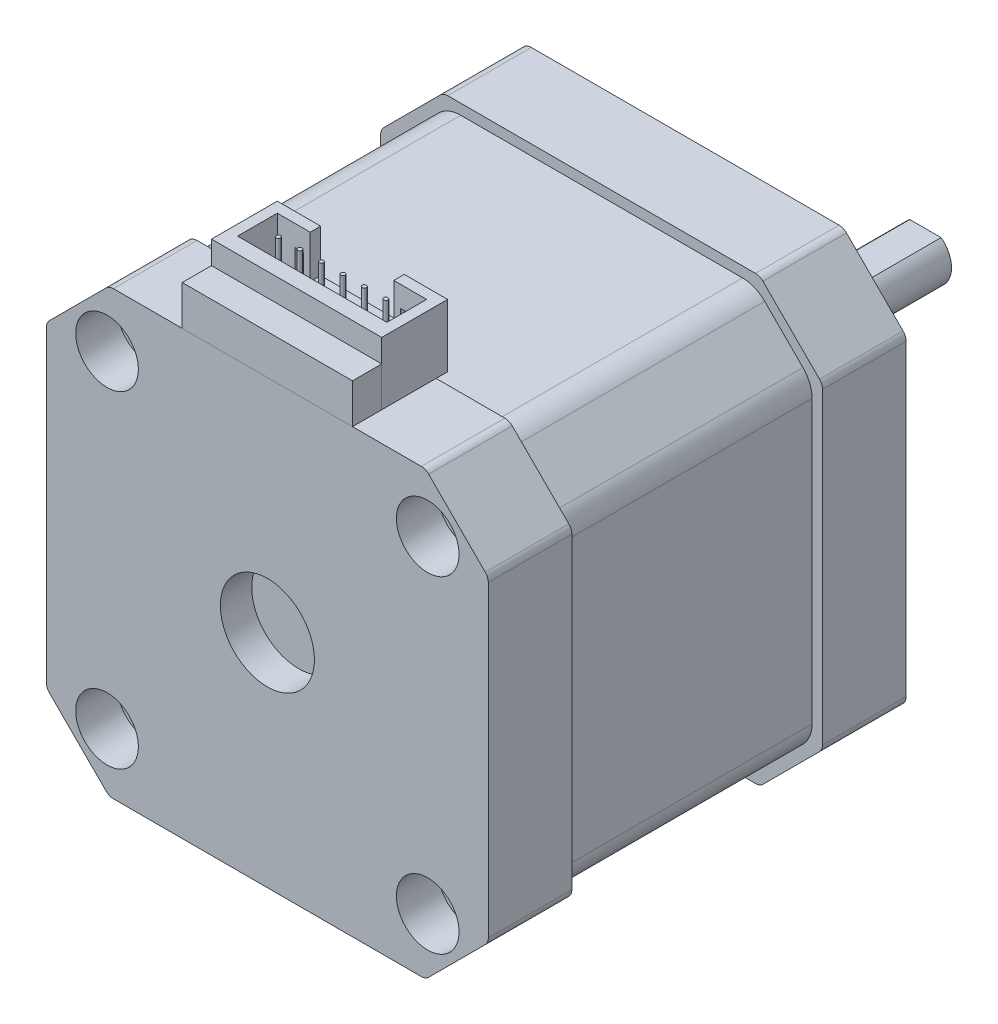
SolidWorks part; units mm, degrees
ref_plane "Front Plane" through (0, 0, 0) normal (0, 0, 1) x (1, 0, 0)
ref_plane "Top Plane" through (0, 0, 0) normal (0, 1, 0) x (1, 0, 0)
ref_plane "Right Plane" through (0, 0, 0) normal (1, 0, 0) x (0, 0, -1)
sketch "Sketch1" plane through (0, 0, 0) normal (0, 0, 1) x (1, 0, 0)
  line L1 (-21.15, 21.15) -> (21.15, 21.15)
  line L2 (-21.15, 21.15) -> (-21.15, -21.15)
  line L3 (-21.15, -21.15) -> (21.15, -21.15)
  line L4 (21.15, 21.15) -> (21.15, -21.15)
  line L5 (-21.15, 21.15) -> (21.15, -21.15) construction
  line L6 (-21.15, -21.15) -> (21.15, 21.15) construction
  point P0 (0, 0)
  dimension "D1" = 42.3
  dimension "D2" = 42.3
extrude "Boss-Extrude1" add sketch "Sketch1" along normal blind 8
chamfer "Chamfer1" distance 6 angle 45 4 edges at (-21.15, -21.15, 4) (21.15, -21.15, 4) (21.15, 21.15, 4) (-21.15, 21.15, 4)
fillet "Fillet1" radius 1 8 edges at (-15.15, 21.15, 4) (-21.15, 15.15, 4) (-21.15, -15.15, 4) (-15.15, -21.15, 4) (15.15, -21.15, 4) (21.15, -15.15, 4) (21.15, 15.15, 4) (15.15, 21.15, 4)
sketch "Sketch3" plane through (0, 0, 0) normal (0, 0, -1) x (-1, 0, 0)
  line L0 (-14.7358, 21.15) -> (14.7358, 21.15) construction
  line L1 (-15.4429, 20.8571) -> (-20.8571, 15.4429) construction
  line L2 (-21.15, -14.7358) -> (-21.15, 14.7358) construction
  line L3 (20.8571, 15.4429) -> (15.4429, 20.8571) construction
  line L4 (21.15, 14.7358) -> (21.15, -14.7358) construction
  line L5 (15.4429, -20.8571) -> (20.8571, -15.4429) construction
  line L6 (14.7358, -21.15) -> (-14.7358, -21.15) construction
  line L7 (-20.8571, -15.4429) -> (-15.4429, -20.8571) construction
  line L8 (-14.7358, 21.15) -> (14.7358, 21.15)
  line L9 (-15.4429, 20.8571) -> (-20.8571, 15.4429)
  line L10 (-21.15, -14.7358) -> (-21.15, 14.7358)
  line L11 (20.8571, 15.4429) -> (15.4429, 20.8571)
  line L12 (21.15, 14.7358) -> (21.15, -14.7358)
  line L13 (15.4429, -20.8571) -> (20.8571, -15.4429)
  line L14 (14.7358, -21.15) -> (-14.7358, -21.15)
  line L15 (-20.8571, -15.4429) -> (-15.4429, -20.8571)
  line L16 (-14.7358, 20.15) -> (14.7358, 20.15)
  line L17 (20.15, 14.7358) -> (14.7358, 20.15)
  line L18 (20.15, 14.7358) -> (20.15, -14.7358)
  line L19 (14.7358, -20.15) -> (20.15, -14.7358)
  line L20 (14.7358, -20.15) -> (-14.7358, -20.15)
  line L21 (-20.15, -14.7358) -> (-14.7358, -20.15)
  line L22 (-20.15, -14.7358) -> (-20.15, 14.7358)
  line L23 (-14.7358, 20.15) -> (-20.15, 14.7358)
  arc A0 (20.8571, -15.4429) -> (21.15, -14.7358) centre (20.15, -14.7358) ccw construction
  arc A1 (14.7358, -21.15) -> (15.4429, -20.8571) centre (14.7358, -20.15) ccw construction
  arc A2 (-15.4429, -20.8571) -> (-14.7358, -21.15) centre (-14.7358, -20.15) ccw construction
  arc A3 (-21.15, -14.7358) -> (-20.8571, -15.4429) centre (-20.15, -14.7358) ccw construction
  arc A4 (15.4429, 20.8571) -> (14.7358, 21.15) centre (14.7358, 20.15) ccw construction
  arc A5 (21.15, 14.7358) -> (20.8571, 15.4429) centre (20.15, 14.7358) ccw construction
  arc A6 (-14.7358, 21.15) -> (-15.4429, 20.8571) centre (-14.7358, 20.15) ccw construction
  arc A7 (-20.8571, 15.4429) -> (-21.15, 14.7358) centre (-20.15, 14.7358) ccw construction
  arc A8 (20.8571, -15.4429) -> (21.15, -14.7358) centre (20.15, -14.7358) ccw
  arc A9 (14.7358, -21.15) -> (15.4429, -20.8571) centre (14.7358, -20.15) ccw
  arc A10 (-15.4429, -20.8571) -> (-14.7358, -21.15) centre (-14.7358, -20.15) ccw
  arc A11 (-21.15, -14.7358) -> (-20.8571, -15.4429) centre (-20.15, -14.7358) ccw
  arc A12 (15.4429, 20.8571) -> (14.7358, 21.15) centre (14.7358, 20.15) ccw
  arc A13 (21.15, 14.7358) -> (20.8571, 15.4429) centre (20.15, 14.7358) ccw
  arc A14 (-14.7358, 21.15) -> (-15.4429, 20.8571) centre (-14.7358, 20.15) ccw
  arc A15 (-20.8571, 15.4429) -> (-21.15, 14.7358) centre (-20.15, 14.7358) ccw
  arc A16 (14.7358, 20.15) -> (14.7358, 20.15) centre (14.7358, 20.15) ccw
  arc A17 (20.15, 14.7358) -> (20.15, 14.7358) centre (20.15, 14.7358) ccw
  arc A18 (20.15, -14.7358) -> (20.15, -14.7358) centre (20.15, -14.7358) ccw
  arc A19 (14.7358, -20.15) -> (14.7358, -20.15) centre (14.7358, -20.15) ccw
  arc A20 (-14.7358, -20.15) -> (-14.7358, -20.15) centre (-14.7358, -20.15) ccw
  arc A21 (-20.15, -14.7358) -> (-20.15, -14.7358) centre (-20.15, -14.7358) ccw
  arc A22 (-20.15, 14.7358) -> (-20.15, 14.7358) centre (-20.15, 14.7358) ccw
  arc A23 (-14.7358, 20.15) -> (-14.7358, 20.15) centre (-14.7358, 20.15) ccw
  dimension "D1" = 1
extrude "Boss-Extrude4" add sketch "Sketch3" along normal blind 24 separate body contours L16 A16 L17 A17 L18 A18 L19 A19 L20 A20 L21 A21 L22 A22 L23 A23
fillet "Fillet2" radius 3 8 edges at (20.15, -14.7358, -12) (14.7358, -20.15, -12) (-14.7358, -20.15, -12) (-20.15, -14.7358, -12) (-20.15, 14.7358, -12) (-14.7358, 20.15, -12) (20.15, 14.7358, -12) (14.7358, 20.15, -12)
sketch "Sketch6" plane through (0, 0, -24) normal (0, 0, -1) x (-1, 0, 0)
  line L0 (15.4429, -20.8571) -> (20.8571, -15.4429) construction
  line L1 (14.7358, -21.15) -> (-14.7358, -21.15) construction
  line L2 (-20.8571, -15.4429) -> (-15.4429, -20.8571) construction
  line L3 (-21.15, -14.7358) -> (-21.15, 14.7358) construction
  line L4 (-15.4429, 20.8571) -> (-20.8571, 15.4429) construction
  line L5 (-14.7358, 21.15) -> (14.7358, 21.15) construction
  line L6 (20.8571, 15.4429) -> (15.4429, 20.8571) construction
  line L7 (21.15, 14.7358) -> (21.15, -14.7358) construction
  line L8 (15.4429, -20.8571) -> (20.8571, -15.4429)
  line L9 (14.7358, -21.15) -> (-14.7358, -21.15)
  line L10 (-20.8571, -15.4429) -> (-15.4429, -20.8571)
  line L11 (-21.15, -14.7358) -> (-21.15, 14.7358)
  line L12 (-15.4429, 20.8571) -> (-20.8571, 15.4429)
  line L13 (-14.7358, 21.15) -> (14.7358, 21.15)
  line L14 (20.8571, 15.4429) -> (15.4429, 20.8571)
  line L15 (21.15, 14.7358) -> (21.15, -14.7358)
  arc A0 (20.8571, -15.4429) -> (21.15, -14.7358) centre (20.15, -14.7358) ccw construction
  arc A1 (14.7358, -21.15) -> (15.4429, -20.8571) centre (14.7358, -20.15) ccw construction
  arc A2 (-15.4429, -20.8571) -> (-14.7358, -21.15) centre (-14.7358, -20.15) ccw construction
  arc A3 (-21.15, -14.7358) -> (-20.8571, -15.4429) centre (-20.15, -14.7358) ccw construction
  arc A4 (-20.8571, 15.4429) -> (-21.15, 14.7358) centre (-20.15, 14.7358) ccw construction
  arc A5 (-14.7358, 21.15) -> (-15.4429, 20.8571) centre (-14.7358, 20.15) ccw construction
  arc A6 (15.4429, 20.8571) -> (14.7358, 21.15) centre (14.7358, 20.15) ccw construction
  arc A7 (21.15, 14.7358) -> (20.8571, 15.4429) centre (20.15, 14.7358) ccw construction
  arc A8 (20.8571, -15.4429) -> (21.15, -14.7358) centre (20.15, -14.7358) ccw
  arc A9 (14.7358, -21.15) -> (15.4429, -20.8571) centre (14.7358, -20.15) ccw
  arc A10 (-15.4429, -20.8571) -> (-14.7358, -21.15) centre (-14.7358, -20.15) ccw
  arc A11 (-21.15, -14.7358) -> (-20.8571, -15.4429) centre (-20.15, -14.7358) ccw
  arc A12 (-20.8571, 15.4429) -> (-21.15, 14.7358) centre (-20.15, 14.7358) ccw
  arc A13 (-14.7358, 21.15) -> (-15.4429, 20.8571) centre (-14.7358, 20.15) ccw
  arc A14 (15.4429, 20.8571) -> (14.7358, 21.15) centre (14.7358, 20.15) ccw
  arc A15 (21.15, 14.7358) -> (20.8571, 15.4429) centre (20.15, 14.7358) ccw
extrude "Boss-Extrude5" add sketch "Sketch6" along normal blind 8 separate body
sketch "Sketch7" plane through (0, 0, 8) normal (0, 0, 1) x (1, 0, 0)
  line L0 (-15.35, 15.65) -> (15.35, 15.65) construction
  line L1 (-15.35, -15.65) -> (15.35, -15.65) construction
  line L2 (14.7358, 21.15) -> (-14.7358, 21.15) construction
  line L3 (15.35, 15.65) -> (20.65, 15.65) construction
  line L4 (20.8571, 15.4429) -> (15.4429, 20.8571) construction
  line L5 (-15.35, 15.65) -> (-20.65, 15.65) construction
  line L6 (-15.4429, 20.8571) -> (-20.8571, 15.4429) construction
  line L7 (-14.7358, -21.15) -> (14.7358, -21.15) construction
  circle A0 centre (-15.35, 15.65) radius 1.5
  circle A1 centre (15.35, 15.65) radius 1.5
  circle A2 centre (15.35, -15.65) radius 1.5
  circle A3 centre (-15.35, -15.65) radius 1.5
  dimension "D1" = 30.7
  dimension "D2" = 3
  dimension "D3" = 5.5
  dimension "D4" = 5.5
extrude "Cut-Extrude1" cut sketch "Sketch7" against normal through all
sketch "Sketch8" plane through (0, 0, -32) normal (0, 0, -1) x (-1, 0, 0)
  circle A0 centre (0, 0) radius 4.5
  dimension "D1" = 9
extrude "Cut-Extrude2" cut sketch "Sketch8" against normal through all
sketch "Sketch9" plane through (0, 0, -32) normal (0, 0, -1) x (-1, 0, 0)
  circle A0 centre (0, 0) radius 11
  circle A1 centre (0, 0) radius 4.5 construction
  circle A2 centre (0, 0) radius 4.5
  dimension "D1" = 22
extrude "Boss-Extrude7" add sketch "Sketch9" along normal blind 1.8
fillet "Fillet4" radius 0.5 1 edges at (-11, 0, -32)
fillet "Fillet5" radius 0.2 1 edges at (-11, 0, -33.8)
ref_plane "Plane2" through (0, 0, 5) normal (0, 0, 1) x (1, 0, 0)
sketch "Sketch12" plane through (0, 0, 5) normal (0, 0, 1) x (1, 0, 0)
  circle A0 centre (0, 0) radius 4.5 construction
  circle A1 centre (0, 0) radius 4.5
extrude "Boss-Extrude8" add sketch "Sketch12" against normal blind 10 separate body
sketch "Sketch16" plane through (0, 0, -5) normal (0, 0, -1) x (-1, 0, 0)
  circle A0 centre (0, 0) radius 2.5
  dimension "D1" = 5
extrude "Boss-Extrude9" add sketch "Sketch16" along normal blind 50
sketch "Sketch17" plane through (0, 0, -55) normal (0, 0, -1) x (-1, 0, 0)
  line L1 (-1.5, 2) -> (1.5, 2)
  arc A1 (1.5, 2) -> (-1.5, 2) centre (0, 0) ccw
  dimension "D1" = 5
  dimension "D2" = 2
extrude "Cut-Extrude10" cut sketch "Sketch17" against normal blind 20
sketch "Sketch24" plane through (0, 0, 8) normal (0, 0, 1) x (1, 0, 0)
  line L0 (14.7358, 21.15) -> (-14.7358, 21.15) construction
  line L1 (-8.15, 24.95) -> (8.15, 24.95)
  line L2 (-8.15, 24.95) -> (-8.15, 21.15)
  line L3 (-8.15, 21.15) -> (8.15, 21.15)
  line L4 (8.15, 24.95) -> (8.15, 21.15)
  line L5 (-8.15, 21.15) -> (-14.7358, 21.15) construction
  line L6 (8.15, 21.15) -> (14.7358, 21.15) construction
  dimension "D1" = 16.3
  dimension "D2" = 3.8
extrude "Boss-Extrude17" add sketch "Sketch24" against normal blind 2.8 separate body
sketch "Sketch25" plane through (0, 0, 5.2) normal (0, 0, -1) x (-1, 0, 0)
  line L0 (8.15, 21.15) -> (-8.15, 21.15) construction
  line L1 (-8.15, 27.15) -> (8.15, 27.15)
  line L2 (-8.15, 27.15) -> (-8.15, 21.15)
  line L3 (-8.15, 21.15) -> (8.15, 21.15)
  line L4 (8.15, 27.15) -> (8.15, 21.15)
  dimension "D1" = 6
extrude "Boss-Extrude18" add sketch "Sketch25" along normal blind 6.3 separate body
sketch "Sketch26" plane through (0, 0, -1.1) normal (0, 0, -1) x (-1, 0, 0)
  line L0 (-8.15, 21.15) -> (-8.15, 27.15)
  line L1 (-8.15, 27.15) -> (-4, 27.15)
  line L2 (8.15, 27.15) -> (-8.15, 27.15) construction
  line L3 (-4, 27.15) -> (-4, 23.05)
  line L4 (-4, 23.05) -> (4, 23.05)
  line L5 (4, 23.05) -> (4, 27.15)
  line L6 (4, 27.15) -> (8.15, 27.15)
  line L7 (8.15, 27.15) -> (8.15, 21.15)
  line L8 (8.15, 21.15) -> (5.45, 21.15)
  line L9 (-8.15, 21.15) -> (8.15, 21.15) construction
  line L10 (5.45, 21.15) -> (5.45, 25.15)
  line L11 (5.45, 25.15) -> (4.65, 25.15)
  line L12 (4.65, 25.15) -> (4.65, 21.65)
  line L13 (4.65, 21.65) -> (-4.65, 21.65)
  line L14 (-4.65, 21.65) -> (-4.65, 25.15)
  line L15 (-4.65, 25.15) -> (-5.45, 25.15)
  line L16 (-5.45, 25.15) -> (-5.45, 21.15)
  line L17 (14.7358, 21.15) -> (-14.7358, 21.15) construction
  line L18 (-8.15, 21.15) -> (-5.45, 21.15)
  line L19 (-5.45, 21.15) -> (5.45, 21.15)
  line L20 (-4, 27.15) -> (4, 27.15)
  line M17 (-8.15, 21.15) -> (8.15, 21.15)
  line M19 (8.15, 27.15) -> (-8.15, 27.15)
  dimension "D1" = 3.5
  dimension "D2" = 3.5
  dimension "D3" = 8
  dimension "D4" = 1.4
  dimension "D5" = 0.8
  dimension "D6" = 0.5
  dimension "D7" = 2
extrude "Cut-Extrude6" cut sketch "Sketch26" against normal blind 4 contours L4 L5 L3 M19 region at (0, 25.1, -1.1)
sketch "Sketch28" plane through (0, 27.15, 0) normal (0, 1, 0) x (1, 0, 0)
  line L0 (-8.15, -5.2) -> (8.15, -5.2) construction
  line L1 (-7.15, 0.1) -> (7.15, 0.1)
  line L2 (-7.15, 0.1) -> (-7.15, -3.7)
  line L3 (-7.15, -3.7) -> (7.15, -3.7)
  line L4 (7.15, 0.1) -> (7.15, -3.7)
  line L5 (4, 1.1) -> (8.15, 1.1) construction
  line L6 (8.15, 1.1) -> (8.15, -5.2) construction
  line L7 (-8.15, 1.1) -> (-8.15, -5.2) construction
  dimension "D1" = 1.5
  dimension "D2" = 1
  dimension "D3" = 1
  dimension "D4" = 1
extrude "Cut-Extrude7" cut sketch "Sketch28" against normal blind 5
extrude "Cut-Extrude8" cut sketch "Sketch26<4>" against normal blind 1 contours L15 L16 L10 L11 L12 L13 L14 M17 region at (5.3339, 23.15, -1.1)
sketch "Sketch26<4>" plane through (0, 0, -1.1) normal (0, 0, -1) x (-1, 0, 0) same geometry as "Sketch26"
sketch "Sketch29" plane through (0, 22.15, 0) normal (0, 1, 0) x (1, 0, 0)
  line L0 (-5.147, -1.8) -> (-5.147, 0.1) construction
  line L1 (-4, 0.1) -> (-7.15, 0.1) construction
  line L2 (-5.147, -1.8) -> (-5.147, -3.7) construction
  line L3 (-7.15, -3.7) -> (7.15, -3.7) construction
  line L4 (5.147, -1.8) -> (7.15, -1.8) construction
  line L5 (7.15, -3.7) -> (7.15, 0.1) construction
  line L6 (-5.147, -1.8) -> (-7.15, -1.8) construction
  line L7 (-7.15, 0.1) -> (-7.15, -3.7) construction
  circle A0 centre (-5.147, -1.8) radius 0.2
  circle A1 centre (-3.0882, -1.8) radius 0.2
  circle A2 centre (-1.0294, -1.8) radius 0.2
  circle A3 centre (1.0294, -1.8) radius 0.2
  circle A4 centre (3.0882, -1.8) radius 0.2
  circle A5 centre (5.147, -1.8) radius 0.2
  dimension "D1" = 0.4
  dimension "D3" = 2.0588
  dimension "D2" = 6
extrude "Boss-Extrude19" add sketch "Sketch29" along normal blind 5
sketch "Sketch30" plane through (0, 0, 8) normal (0, 0, 1) x (1, 0, 0)
  circle A0 centre (-15.35, 15.65) radius 3
  circle A1 centre (15.35, 15.65) radius 3
  circle A2 centre (15.35, -15.65) radius 3
  circle A3 centre (-15.35, -15.65) radius 3
  circle A4 centre (-15.35, 15.65) radius 1.5 construction
  circle A5 centre (15.35, 15.65) radius 1.5 construction
  circle A6 centre (15.35, -15.65) radius 1.5 construction
  circle A7 centre (-15.35, -15.65) radius 1.5 construction
  circle A8 centre (-15.35, 15.65) radius 1.5
  circle A9 centre (15.35, 15.65) radius 1.5
  circle A10 centre (15.35, -15.65) radius 1.5
  circle A11 centre (-15.35, -15.65) radius 1.5
  dimension "D1" = 6
extrude "Cut-Extrude9" cut sketch "Sketch30" against normal blind 4
ref_plane "Plane3" through (0, 0, 4) normal (0, 0, 1) x (1, 0, 0)
